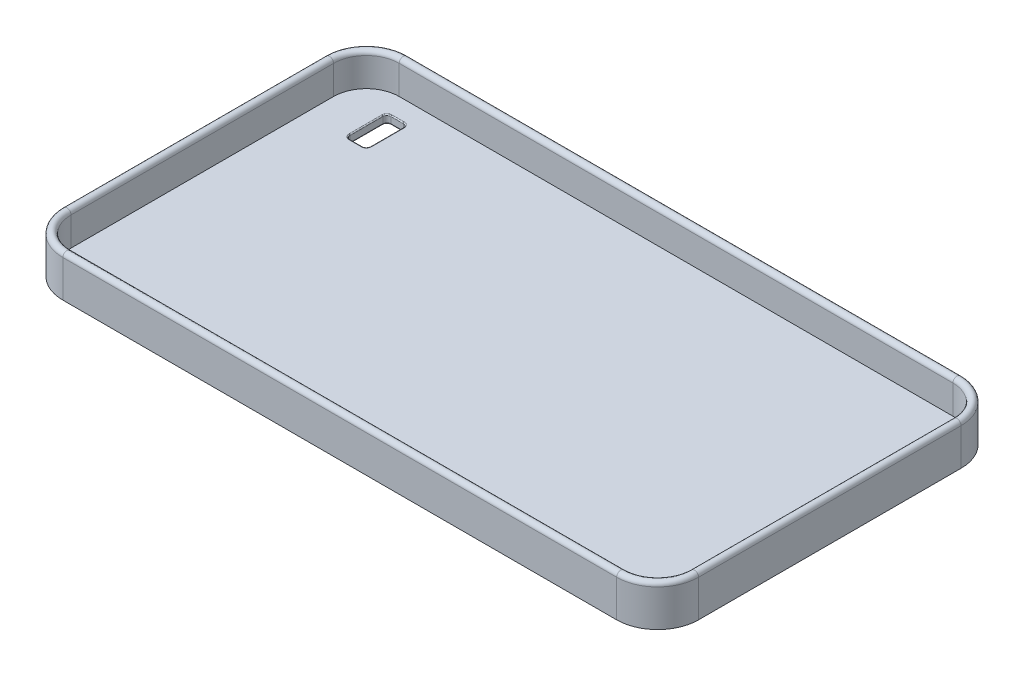
SolidWorks part; units mm, degrees
ref_plane "Front" through (0, 0, 0) normal (0, 0, 1) x (1, 0, 0)
ref_plane "Top" through (0, 0, 0) normal (0, 1, 0) x (1, 0, 0)
ref_plane "Right" through (0, 0, 0) normal (1, 0, 0) x (0, 0, -1)
sketch "Sketch1" plane through (0, 0, 0) normal (0, 1, 0) x (1, 0, 0)
  line L1 (-77.5, -42) -> (77.5, -42)
  line L2 (-77.5, -42) -> (-77.5, 42)
  line L3 (-77.5, 42) -> (77.5, 42)
  line L4 (77.5, -42) -> (77.5, 42)
  line L5 (-77.5, -42) -> (77.5, 42) construction
  line L6 (-77.5, 42) -> (77.5, -42) construction
  point P0 (0, 0)
  dimension "D1" = 155
  dimension "D2" = 84
extrude "Boss-Extrude1" add sketch "Sketch1" along normal blind 10
fillet "Fillet1" radius 10 4 edges at (-77.5, 5, 42) (-77.5, 5, -42) (77.5, 5, -42) (77.5, 5, 42)
shell "Shell1" thickness 2 removed face at (0, 10, 0)
sketch "Sketch2" plane through (0, 2, 0) normal (0, 1, 0) x (1, 0, 0)
  line L0 (67.5, 40) -> (-67.5, 40) construction
  line L1 (-65.5, 35) -> (-60.5, 35)
  line L2 (-65.5, 35) -> (-65.5, 25)
  line L3 (-65.5, 25) -> (-60.5, 25)
  line L4 (-60.5, 35) -> (-60.5, 25)
  line L5 (-65.5, 35) -> (-60.5, 25) construction
  line L6 (-65.5, 25) -> (-60.5, 35) construction
  line L7 (-75.5, 32) -> (-75.5, -32) construction
  point P0 (-63, 30)
  dimension "D1" = 10
  dimension "D2" = 12.5
  dimension "D3" = 10
  dimension "D4" = 5
extrude "Cut-Extrude1" cut sketch "Sketch2" against normal through all
fillet "Fillet2" radius 1 4 edges at (-60.5, 1, -25) (-65.5, 1, -25) (-65.5, 1, -35) (-60.5, 1, -35)
fillet "Fillet3" radius 0.25 16 edges at (-60.7929, 0, -34.7071) (-60.5, 0, -30) (-60.7929, 0, -25.2929) (-63, 0, -25) (-65.2071, 0, -25.2929) (-65.5, 0, -30) (-65.2071, 0, -34.7071) (-65.2071, 2, -34.7071) (-63, 2, -35) (-60.7929, 2, -34.7071) (-60.5, 2, -30) (-60.7929, 2, -25.2929) (-63, 2, -25) (-65.2071, 2, -25.2929) (-63, 0, -35) (-65.5, 2, -30)
fillet "Fillet4" 2 edges at (-77.5, 10, 0) (-75.5, 10, 0) type full round first side face at (-77.5, 5, 0) second side face at (-75.5, 6, 0) middle face at (0, 10, 0)
